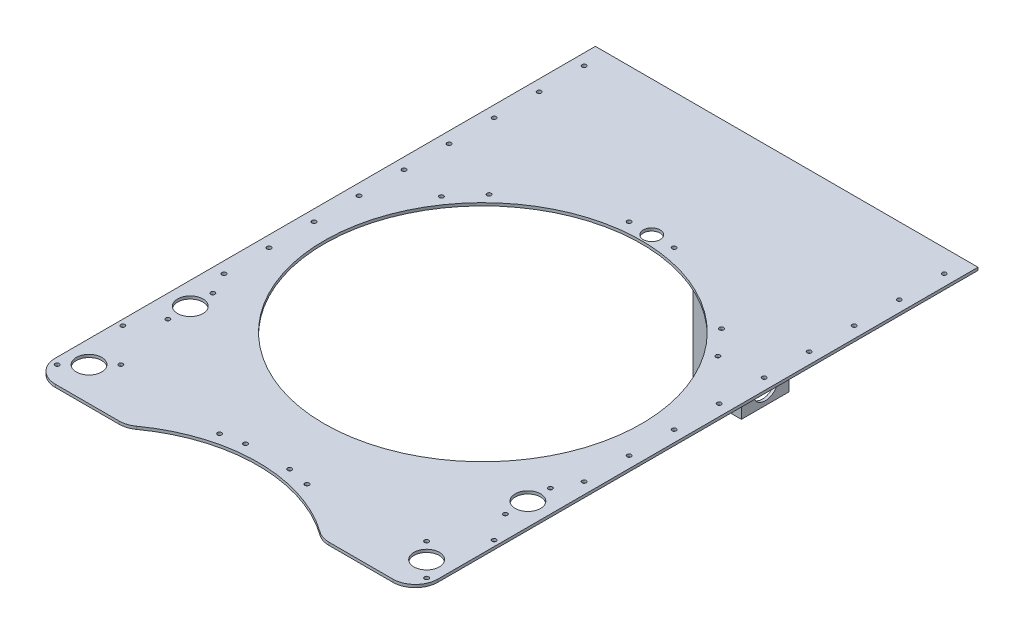
SolidWorks part; units mm, degrees
material "6063-T1"
ref_plane "Front Plane" through (0, 0, 0) normal (0, 0, 1) x (1, 0, 0)
ref_plane "Top Plane" through (0, 0, 0) normal (0, 1, 0) x (1, 0, 0)
ref_plane "Right Plane" through (0, 0, 0) normal (1, 0, 0) x (0, 0, -1)
sketch "Sketch1" plane through (0, 0, 0) normal (0, 1, 0) x (1, 0, 0)
  line L1 (-215.9, 342.9) -> (215.9, 342.9)
  line L2 (-215.9, 342.9) -> (-215.9, -342.9)
  line L3 (-215.9, -342.9) -> (215.9, -342.9)
  line L4 (215.9, 342.9) -> (215.9, -342.9)
  line L5 (-215.9, 342.9) -> (215.9, -342.9) construction
  line L6 (-215.9, -342.9) -> (215.9, 342.9) construction
  point P0 (0, 0)
  dimension "D1" = 431.8
  dimension "D2" = 685.8
extrude "Boss-Extrude1" add sketch "Sketch1" along normal blind 3.175
sketch "Sketch2" plane through (0, 3.175, 0) normal (0, 1, 0) x (1, 0, 0)
  line L0 (0, -342.9) -> (0, 342.9) construction
  line L1 (-215.9, -342.9) -> (215.9, -342.9) construction
  line L2 (215.9, 342.9) -> (-215.9, 342.9) construction
  line L3 (-215.9, 342.9) -> (-215.9, -342.9) construction
  line L4 (-208.4605, -322.7605) -> (-190.5, -304.8) construction
  line L5 (-193.1461, -304.8) -> (-215.9, -304.8) construction
  circle A0 centre (-190.5, -304.8) radius 14.3129
  circle A1 centre (-190.5, -190.5) radius 14.3129
  circle A3 centre (190.5, -190.5) radius 14.3129
  circle A4 centre (190.5, -190.5) radius 25.4 construction
  circle A5 centre (-190.5, -190.5) radius 25.4 construction
  circle A6 centre (190.5, -215.9) radius 2.3813
  circle A7 centre (190.5, -165.1) radius 2.3813
  circle A8 centre (-190.5, -215.9) radius 2.3813
  circle A9 centre (-190.5, -165.1) radius 2.3813
  circle A10 centre (-190.5, -304.8) radius 25.4 construction
  circle A11 centre (-208.4605, -322.7605) radius 2.3813
  circle A15 centre (-172.5395, -286.8395) radius 2.3813
  circle A16 centre (172.5395, -286.8395) radius 2.3813
  circle A17 centre (208.4605, -322.7605) radius 2.3813
  circle A18 centre (190.5, -304.8) radius 14.3129
  point P33 (-190.5, -304.8)
  point P34 (-190.5, -304.8)
  dimension "D1" = 28.6258
  dimension "D2" = 28.6258
  dimension "D6" = 50.8
  dimension "D7" = 50.8
  dimension "D8" = 4.7625
  dimension "D9" = 4.7625
  dimension "D10" = 4.7625
  dimension "D11" = 4.7625
  dimension "D12" = 50.8
  dimension "D13" = 4.7625
  dimension "D3" = 38.1
  dimension "D4" = 114.3
  dimension "D5" = 25.4
  dimension "D15" = 45
  dimension "D14" = 2
extrude "Cut-Extrude1" cut sketch "Sketch2" against normal through all
sketch "Sketch3" plane through (0, 0, 0) normal (0, -1, 0) x (-1, 0, 0)
  line L1 (29.8706, 270.2084) -> (-24.7394, 270.2084)
  line L2 (29.8706, 270.2084) -> (29.8706, 216.2334)
  line L3 (29.8706, 216.2334) -> (-24.7394, 216.2334)
  line L4 (-24.7394, 270.2084) -> (-24.7394, 216.2334)
  line L5 (29.8706, 270.2084) -> (-24.7394, 216.2334) construction
  line L6 (29.8706, 216.2334) -> (-24.7394, 270.2084) construction
  point P0 (2.5656, 243.2209)
  dimension "D1" = 53.975
  dimension "D2" = 54.61
extrude "Boss-Extrude2" add sketch "Sketch3" along normal blind 203.2
fillet "Fillet1" [suppressed] radius 20.32
sketch "Sketch4" plane through (0, -203.2, 0) normal (0, -1, 0) x (-1, 0, 0)
  line L0 (-24.7394, 216.2334) -> (29.8706, 216.2334) construction
  line L1 (26.6956, 267.0334) -> (-21.5644, 267.0334)
  line L2 (26.6956, 267.0334) -> (26.6956, 219.4084)
  line L3 (26.6956, 219.4084) -> (-21.5644, 219.4084)
  line L4 (-21.5644, 267.0334) -> (-21.5644, 219.4084)
  line L5 (26.6956, 267.0334) -> (-21.5644, 219.4084) construction
  line L6 (26.6956, 219.4084) -> (-21.5644, 267.0334) construction
  line L7 (29.8706, 270.2084) -> (-24.7394, 270.2084) construction
  line L8 (29.8706, 216.2334) -> (29.8706, 270.2084) construction
  line L9 (-24.7394, 270.2084) -> (-24.7394, 216.2334) construction
  point P0 (2.5656, 243.2209)
  dimension "D1" = 3.175
  dimension "D2" = 3.175
  dimension "D3" = 3.175
  dimension "D4" = 3.175
extrude "Cut-Extrude2" cut sketch "Sketch4" against normal blind 203.2
sketch "Sketch5" plane through (-29.8706, 0, 0) normal (-1, 0, 0) x (0, 0, 1)
  line L0 (-216.2334, -203.2) -> (-216.2334, 0) construction
  line L1 (-216.2334, -203.2) -> (-270.2084, -203.2) construction
  circle A0 centre (-243.2209, -184.15) radius 14.2875
  dimension "D1" = 28.575
  dimension "D2" = 26.9875
  dimension "D3" = 19.05
extrude "Cut-Extrude3" cut sketch "Sketch5" against normal blind 203.2
sketch "Sketch6" plane through (0, 3.175, 0) normal (0, 1, 0) x (1, 0, 0)
  circle A0 centre (0, -50.8) radius 179.07
  dimension "D1" = 358.14
  dimension "D2" = 50.8
extrude "Cut-Extrude4" cut sketch "Sketch6" against normal through all
sketch "Sketch8" plane through (0, 3.175, 0) normal (0, 1, 0) x (1, 0, 0)
  circle A0 centre (0, 139.7) radius 9.525
  circle A2 centre (0, 139.7) radius 25.4 construction
  circle A3 centre (25.4, 139.7) radius 2.3813
  circle A4 centre (-25.4, 139.7) radius 2.3813
  dimension "D1" = 19.05
  dimension "D3" = 50.8
  dimension "D4" = 4.7625
  dimension "D5" = 4.7625
  dimension "D2" = 139.7
extrude "Cut-Extrude6" cut sketch "Sketch8" against normal through all
fillet "Fillet2" radius 25.4 2 edges at (215.9, 1.5875, 342.9) (-215.9, 1.5875, 342.9)
sketch "Sketch10" plane through (0, 3.175, 0) normal (0, 1, 0) x (1, 0, 0)
  line L0 (-215.9, 342.9) -> (-215.9, -317.5) construction
  line L1 (215.9, -317.5) -> (215.9, 342.9) construction
  circle A0 centre (-190.5, 215.9) radius 14.3129
  circle A1 centre (190.5, 215.9) radius 14.3129
  circle A2 centre (-190.5, 215.9) radius 25.4 construction
  circle A3 centre (190.5, 215.9) radius 25.4 construction
  circle A4 centre (190.5, 190.5) radius 2.3813
  circle A5 centre (190.5, 241.3) radius 2.3813
  circle A6 centre (-190.5, 190.5) radius 2.3813
  circle A7 centre (-190.5, 241.3) radius 2.3813
  circle A8 centre (190.5, -190.5) radius 14.3129 construction
  circle A9 centre (-190.5, -190.5) radius 14.3129 construction
  dimension "D1" = 28.6258
  dimension "D2" = 50.8
  dimension "D3" = 28.6258
  dimension "D4" = 50.8
  dimension "D5" = 4.7625
  dimension "D6" = 4.7625
  dimension "D7" = 4.7625
  dimension "D8" = 4.7625
  dimension "D9" = 25.4
  dimension "D10" = 25.4
  dimension "D11" = 406.4
  dimension "D12" = 406.4
extrude "Cut-Extrude8" [suppressed] cut sketch "Sketch10" against normal through all
sketch "Sketch11" plane through (0, 3.175, 0) normal (0, 1, 0) x (1, 0, 0)
  line L0 (0, -50.8) -> (156.0485, 58.4663) construction
  line L6 (0, 0) -> (0, 139.7) construction
  circle A0 centre (0, -50.8) radius 179.07
  circle A1 centre (0, -50.8) radius 179.07 construction
  circle A2 centre (0, -50.8) radius 184.15
  circle A3 centre (0, -50.8) radius 215.9
  circle A4 centre (156.0485, 58.4663) radius 2.3813
  circle A5 centre (131.1838, 87.3342) radius 2.3813
  circle A6 centre (0, -50.8) radius 190.5 construction
  circle A7 centre (-131.1838, 87.3342) radius 2.3813
  circle A8 centre (-156.0485, 58.4663) radius 2.3813
  dimension "D1" = 368.3
  dimension "D6" = 431.8
  dimension "D7" = 381
  dimension "D9" = 4.7625
  dimension "D10" = 4.7625
  dimension "D2" = 55
  dimension "D8" = 38.1
extrude "Cut-Extrude9" cut sketch "Sketch11" against normal through all contours A4 | A5 | A7 | A8 region at (156.0485, 3.175, -58.4663) region at (131.1838, 3.175, -87.3342) region at (-131.1838, 3.175, -87.3342) region at (-156.0485, 3.175, -58.4663)
sketch "Sketch13" plane through (0, 3.175, 0) normal (0, 1, 0) x (1, 0, 0)
  line L0 (-215.9, 342.9) -> (-215.9, -317.5) construction
  line L1 (215.9, 342.9) -> (-215.9, 342.9) construction
  line L2 (0, -342.9) -> (0, 342.9) construction
  line L3 (-190.5, -342.9) -> (190.5, -342.9) construction
  circle A0 centre (-203.2, 317.5) radius 2.3813
  circle A1 centre (-203.2, 266.7) radius 2.3813
  circle A2 centre (-203.2, 215.9) radius 2.3813
  circle A3 centre (-203.2, 165.1) radius 2.3813
  circle A4 centre (-203.2, 114.3) radius 2.3813
  circle A5 centre (-203.2, 63.5) radius 2.3813
  circle A6 centre (-203.2, 12.7) radius 2.3813
  circle A7 centre (-203.2, -38.1) radius 2.3813
  circle A8 centre (-203.2, -88.9) radius 2.3813
  circle A9 centre (-203.2, -139.7) radius 2.3813
  circle A10 centre (203.2, -139.7) radius 2.3813
  circle A11 centre (203.2, 12.7) radius 2.3813
  circle A12 centre (203.2, 63.5) radius 2.3813
  circle A13 centre (203.2, 114.3) radius 2.3813
  circle A14 centre (203.2, 165.1) radius 2.3813
  circle A15 centre (203.2, 266.7) radius 2.3813
  circle A16 centre (203.2, 317.5) radius 2.3813
  circle A17 centre (-25.4, -330.2) radius 2.4664
  circle A20 centre (-50.8, -330.2) radius 2.3078
  circle A21 centre (50.8, -330.2) radius 2.3078
  circle A22 centre (25.4, -330.2) radius 2.4664
  circle A23 centre (203.2, -88.9) radius 2.3813
  circle A24 centre (203.2, -38.1) radius 2.3813
  circle A25 centre (203.2, 215.9) radius 2.3813
  dimension "D1" = 4.7625
  dimension "D2" = 12.7
  dimension "D3" = 25.4
  dimension "D5" = 25.4
  dimension "D6" = 50.8
  dimension "D7" = 12.7
  dimension "D8" = 12.7
  dimension "D4" = 10
extrude "Cut-Extrude10" cut sketch "Sketch13" against normal through all
sketch "Sketch14" plane through (0, 3.175, 0) normal (0, 1, 0) x (1, 0, 0)
  line L0 (215.9, -317.5) -> (215.9, 342.9) construction
  line L1 (0, -342.9) -> (0, -229.87) construction
  line L2 (-190.5, -342.9) -> (190.5, -342.9) construction
  circle A0 centre (209.55, -247.65) radius 2.3813
  circle A1 centre (190.5, -304.8) radius 14.3129 construction
  circle A2 centre (0, -50.8) radius 179.07 construction
  circle A3 centre (-209.55, -247.65) radius 2.3813
  dimension "D1" = 57.15
  dimension "D3" = 4.7625
  dimension "D2" = 6.35
extrude "Cut-Extrude11" cut sketch "Sketch14" against normal through all
sketch "Sketch16" plane through (0, 3.175, 0) normal (0, 1, 0) x (1, 0, 0)
  line L0 (215.9, -317.5) -> (215.9, 342.9) construction
  line L1 (-215.9, 342.9) -> (215.9, 342.9)
  line L2 (-215.9, 342.9) -> (-215.9, 292.1)
  line L3 (-215.9, 292.1) -> (215.9, 292.1)
  line L4 (215.9, 342.9) -> (215.9, 292.1)
  dimension "D1" = 50.8
extrude "Cut-Extrude13" cut sketch "Sketch16" against normal through all
sketch "Sketch17" plane through (0, 0, 0) normal (0, -1, 0) x (-1, 0, 0)
  line L0 (0, -482.6) -> (0, 3.1553) construction
  line L1 (0, -482.6) -> (24.8652, -293.7298) construction
  line L2 (0, -482.6) -> (49.305, -298.5911) construction
  circle A0 centre (0, -482.6) radius 177.8
  circle A1 centre (0, -482.6) radius 190.5 construction
  circle A2 centre (24.8652, -293.7298) radius 2.3813
  circle A3 centre (49.305, -298.5911) radius 2.3813
  circle A4 centre (-24.8652, -293.7298) radius 2.3813
  circle A5 centre (-49.305, -298.5911) radius 2.3813
  dimension "D1" = 355.6
  dimension "D3" = 381
  dimension "D6" = 4.7625
  dimension "D7" = 4.7625
  dimension "D2" = 482.6
  dimension "D4" = 7.5
  dimension "D5" = 15
extrude "Cut-Extrude14" cut sketch "Sketch17" against normal through all
fillet "Fillet3" radius 25.4 2 edges at (109.9852, 1.5875, 342.9) (-109.9852, 1.5875, 342.9)
